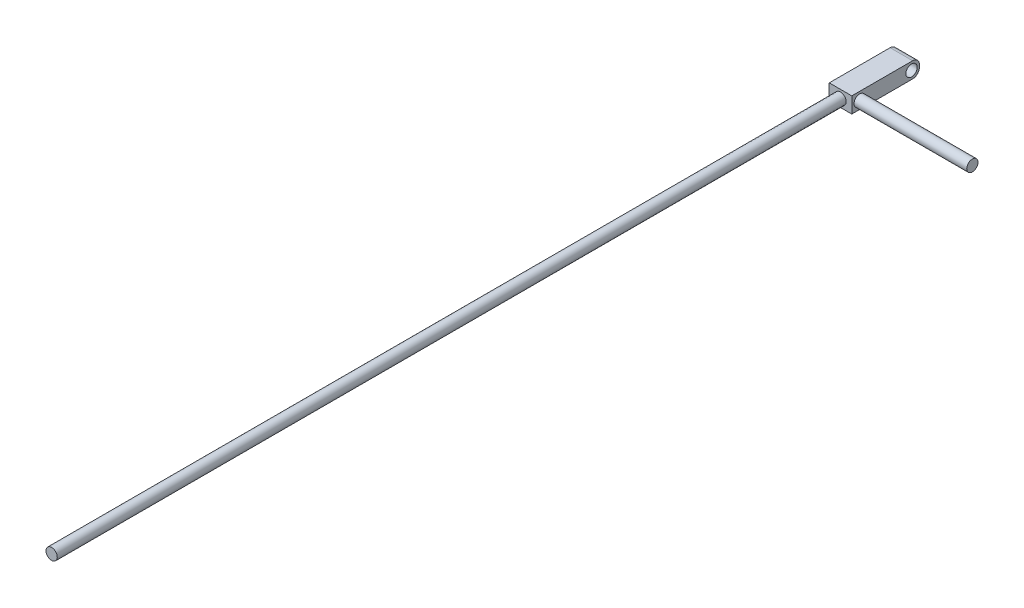
SolidWorks part; units mm, degrees
ref_plane "Front Plane" through (0, 0, 0) normal (0, 0, 1) x (1, 0, 0)
ref_plane "Top Plane" through (0, 0, 0) normal (0, 1, 0) x (1, 0, 0)
ref_plane "Right Plane" through (0, 0, 0) normal (1, 0, 0) x (0, 0, -1)
sketch "Sketch1" plane through (0, 0, 0) normal (0, 0, 1) x (1, 0, 0)
  line L1 (-5, 3.5) -> (5, 3.5)
  line L2 (-5, 3.5) -> (-5, -3.5)
  line L3 (-5, -3.5) -> (5, -3.5)
  line L4 (5, 3.5) -> (5, -3.5)
  line L5 (-5, 3.5) -> (5, -3.5) construction
  line L6 (-5, -3.5) -> (5, 3.5) construction
  point P0 (0, 0)
  dimension "D1" = 10
  dimension "D2" = 7
extrude "Boss-Extrude1" add sketch "Sketch1" along normal blind 30
sketch "Sketch2" plane through (5, 0, 0) normal (1, 0, 0) x (0, 0, -1)
  line L0 (-30, -3.5) -> (-30, 3.5) construction
  line L1 (-30, 3.5) -> (0, 3.5) construction
  circle A0 centre (-3.5, 0) radius 2.5
  circle A1 centre (-26.5, 0) radius 2.5
  dimension "D1" = 5
  dimension "D2" = 5
  dimension "D3" = 23
  dimension "D4" = 3.5
  dimension "D5" = 3.5
  dimension "D6" = 3.5
extrude "Cut-Extrude2" cut sketch "Sketch2" against normal blind 20 contours A0
extrude "Boss-Extrude2" add sketch "Sketch2<3>" along normal blind 50 contours A1
sketch "Sketch2<3>" plane through (5, 0, 0) normal (1, 0, 0) x (0, 0, -1) same geometry as "Sketch2"
fillet "Fillet1" radius 3 2 edges at (0, -3.5, 0) (0, 3.5, 0)
sketch "Sketch3" plane through (0, 0, 30) normal (0, 0, 1) x (1, 0, 0)
  circle A0 centre (0, 0) radius 2.5
extrude "Boss-Extrude3" add sketch "Sketch3" along normal blind 350
